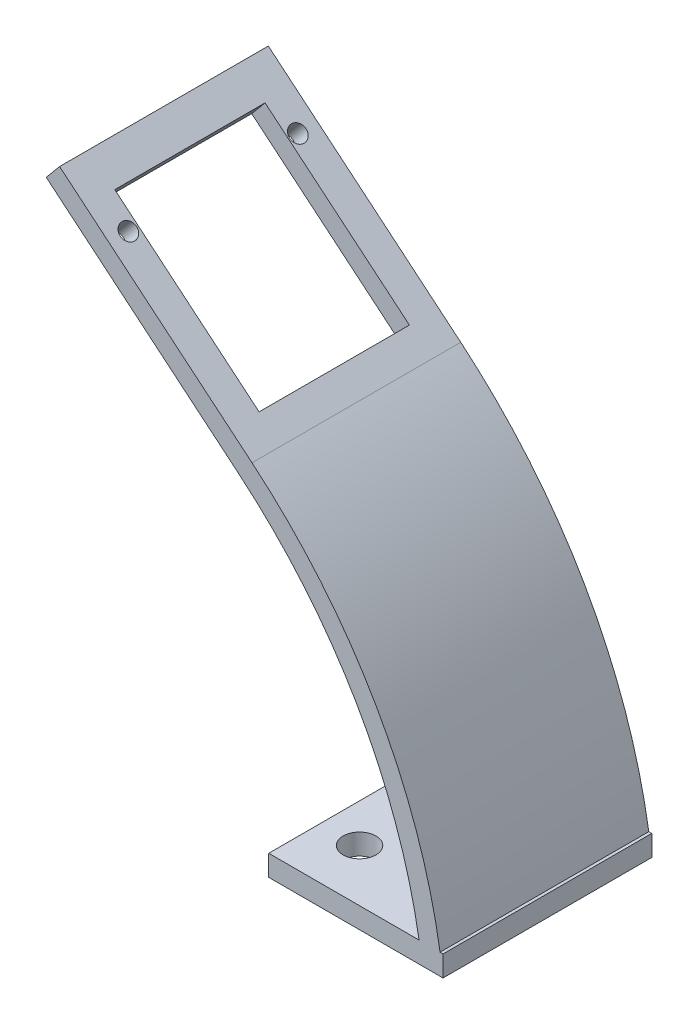
SolidWorks part; units mm, degrees
ref_plane "Front" through (0, 0, 0) normal (0, 0, 1) x (1, 0, 0)
ref_plane "Top" through (0, 0, 0) normal (0, 1, 0) x (1, 0, 0)
ref_plane "Right" through (0, 0, 0) normal (1, 0, 0) x (0, 0, -1)
sketch "Sketch1" plane through (0, 0, 0) normal (0, 0, 1) x (1, 0, 0)
  line L0 (-22.3321, 40.7208) -> (-45.7464, 60.2349)
  line L1 (-45.7464, 60.2349) -> (-44.1203, 62.1861)
  line L2 (-44.1203, 62.1861) -> (-20.706, 42.672)
  line L3 (0, 0) -> (2.54, 0)
  line L4 (55, 0) -> (-55, 0) construction
  arc A0 (0, 0) -> (-22.3321, 40.7208) centre (-62.9865, -8.059) ccw
  arc A1 (-20.706, 42.672) -> (2.54, 0) centre (-62.9399, -8.003) cw
  point P11 (-50.7572, 2.7401)
  point P12 (0, 0)
  dimension "D3" = 63.5
  dimension "D4" = 39.809
  dimension "D1" = 2.54
  dimension "D2" = 2.54
  dimension "D5" = 30.48
  dimension "D6" = 30.48
  dimension "D7" = 42.672
extrude "Boss-Extrude1" add sketch "Sketch1" along normal blind 25.4
sketch "Sketch2" plane through (12.4995, 14.9977, 0) normal (0.6402, 0.7682, 0) x (0.7682, -0.6402, 0)
  line L0 (-73.7058, -25.4) -> (-73.7058, 0) construction
  line L1 (-69.591, -3.556) -> (-46.731, -3.556)
  line L2 (-69.591, -3.556) -> (-69.591, -21.844)
  line L3 (-69.591, -21.844) -> (-46.731, -21.844)
  line L4 (-46.731, -3.556) -> (-46.731, -21.844)
  line L5 (-71.0072, 0) -> (-73.7058, -25.4) construction
  line L6 (-55, 0) -> (55, 0) construction
  line L7 (-72.3565, -12.7) -> (-46.731, -12.7) construction
  line L8 (-43.2258, -25.4) -> (-73.7058, -25.4) construction
  circle A0 centre (-65.8846, -2.4168) radius 0.9995
  circle A1 centre (-65.8896, -23.034) radius 0.9995
  point P12 (-72.3565, -12.7)
  point P13 (-69.591, -12.7)
  point P19 (-65.8896, -1.5082)
  dimension "D4" = 1.999
  dimension "D6" = 20.6172
  dimension "D1" = 22.86
  dimension "D2" = 18.288
  dimension "D3" = 4.1148
  dimension "D5" = 2.366
extrude "Cut-Extrude1" cut sketch "Sketch2" against normal up to next
sketch "Sketch3" plane through (0, 0, 0) normal (0, 1, 0) x (1, 0, 0)
  line L1 (2.54, -25.4) -> (-18.6704, -25.4)
  line L2 (2.54, -25.4) -> (2.54, 0)
  line L3 (2.54, 0) -> (-18.6704, 0)
  line L4 (-18.6704, -25.4) -> (-18.6704, 0)
  circle A0 centre (-13.97, -6.35) radius 2
  circle A1 centre (-13.97, -19.05) radius 2
  point P9 (0, 0)
  point P11 (-13.3169, -4.5958)
  dimension "D1" = 4
  dimension "D2" = 4
  dimension "D5" = 16.51
  dimension "D3" = 12.7
  dimension "D4" = 6.35
extrude "Boss-Extrude2" add sketch "Sketch3" along normal blind 2.54
